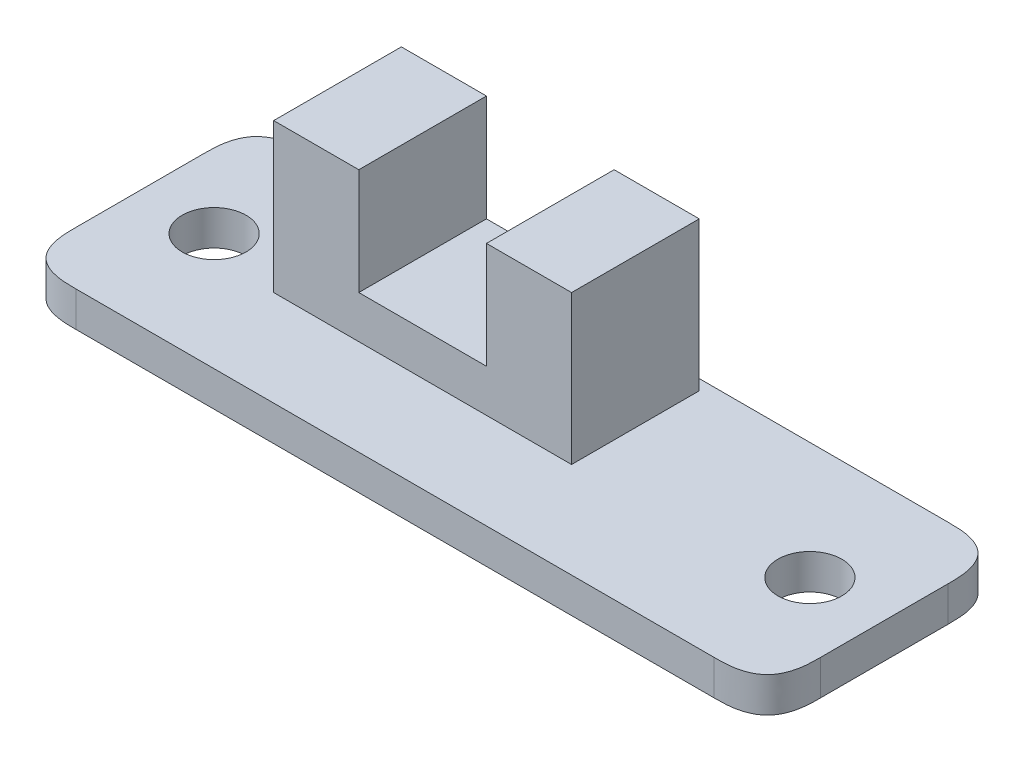
SolidWorks part; units mm, degrees
ref_plane "Front Plane" through (0, 0, 0) normal (0, 0, 1) x (1, 0, 0)
ref_plane "Top Plane" through (0, 0, 0) normal (0, 1, 0) x (1, 0, 0)
ref_plane "Right Plane" through (0, 0, 0) normal (1, 0, 0) x (0, 0, -1)
sketch "Sketch1" plane through (0, 0, 0) normal (0, 1, 0) x (1, 0, 0)
  line L0 (0, 5.5) -> (35, 5.5) construction
  line L1 (0, 0) -> (35, 0)
  line L2 (0, 0) -> (0, 11)
  line L3 (0, 11) -> (35, 11)
  line L4 (35, 0) -> (35, 11)
  line L5 (11.3, 10.5) -> (11.3, 4.5)
  line L6 (7.3, 10.5) -> (21.3, 10.5)
  line L7 (7.3, 10.5) -> (7.3, 4.5)
  line L8 (7.3, 4.5) -> (21.3, 4.5)
  line L9 (21.3, 10.5) -> (21.3, 4.5)
  line L10 (17.3, 10.5) -> (17.3, 4.5)
  circle A0 centre (3.5, 5.5) radius 1.5
  circle A1 centre (31.5, 5.5) radius 1.5
  dimension "D4" = 3
  dimension "D1" = 35
  dimension "D2" = 11
  dimension "D3" = 3.5
  dimension "D6" = 28
  dimension "D7" = 17.7
  dimension "D8" = 4
  dimension "D9" = 11.3
  dimension "D10" = 4
  dimension "D11" = 0.5
  dimension "D12" = 6
  dimension "D5" = 2
extrude "Boss-Extrude1" add sketch "Sketch1" along normal blind 1.65 contours L1 L4 L3 L2 | A0 | A1
fillet "Fillet1" radius 2.5 4 edges at (0, 0.825, -11) (35, 0.825, -11) (0, 0.825, 0) (35, 0.825, 0) curvature continuous yes
extrude "Boss-Extrude2" add sketch "Sketch1<3>" along normal blind 2 from surface contours L8 L9 L6 L7 starting at face at (13.75, 1.65, -4.75)
sketch "Sketch1<3>" plane through (0, 0, 0) normal (0, 1, 0) x (1, 0, 0) same geometry as "Sketch1"
extrude "Boss-Extrude3" add sketch "Sketch1<4>" along normal blind 5 from surface contours L7 L0 L5 L6 | L10 L0 L9 L6 | L0 L7 L8 L5 | L0 L10 L8 L9 region at (19.3, 0, -5) region at (19.3, 0, -8) region at (9.3, 0, -5) region at (9.3, 0, -8) starting at face at (14.3, 3.65, -7.5)
sketch "Sketch1<4>" plane through (0, 0, 0) normal (0, 1, 0) x (1, 0, 0) same geometry as "Sketch1"
